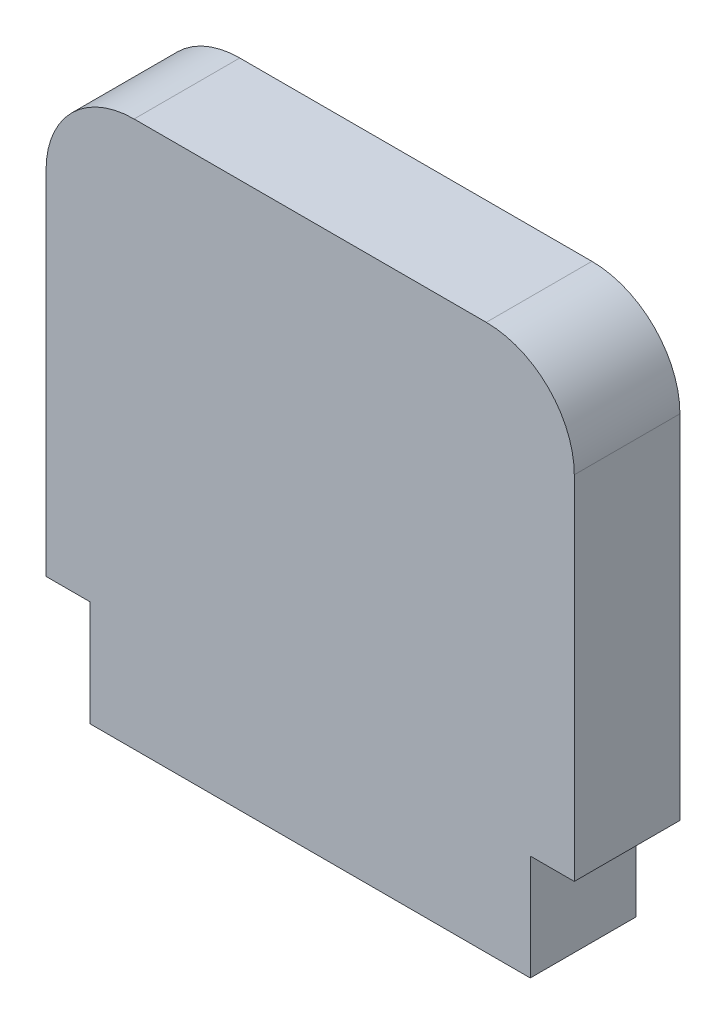
SolidWorks part; units mm, degrees
ref_plane "Plano frontal" through (0, 0, 0) normal (0, 0, 1) x (1, 0, 0)
ref_plane "Plano superior" through (0, 0, 0) normal (0, 1, 0) x (1, 0, 0)
ref_plane "Plano direito" through (0, 0, 0) normal (1, 0, 0) x (0, 0, -1)
sketch "Esboço1" plane through (0, 0, 0) normal (0, 0, 1) x (1, 0, 0)
  line L1 (-15, -12.5) -> (15, -12.5)
  line L2 (-15, -12.5) -> (-15, 12.5)
  line L3 (-15, 12.5) -> (15, 12.5)
  line L4 (15, -12.5) -> (15, 12.5)
  line L5 (0, 12.5) -> (0, -12.5) construction
  line L6 (-15, 0) -> (15, 0) construction
  line L7 (12.5, -18.5) -> (-12.5, -18.5)
  line L8 (12.5, -18.5) -> (12.5, -12.5)
  line L9 (12.5, -12.5) -> (-12.5, -12.5)
  line L10 (-12.5, -18.5) -> (-12.5, -12.5)
  line L11 (0, -12.5) -> (0, -18.5) construction
  line L12 (12.5, -15.5) -> (-12.5, -15.5) construction
  point P0 (0, 0)
  point P4 (0, -15.5)
  dimension "D1" = 6
  dimension "D2" = 25
  dimension "D3" = 30
  dimension "D4" = 25
extrude "Ressalto-extrusão1" add sketch "Esboço1" along normal blind 6 contours L1 L4 L3 L2 | L10 L7 L8 L1 region at (0, 0, 0) region at (0, -15.5, 0)
fillet "Filete1" radius 5 2 edges at (15, 12.5, 3) (-15, 12.5, 3)
